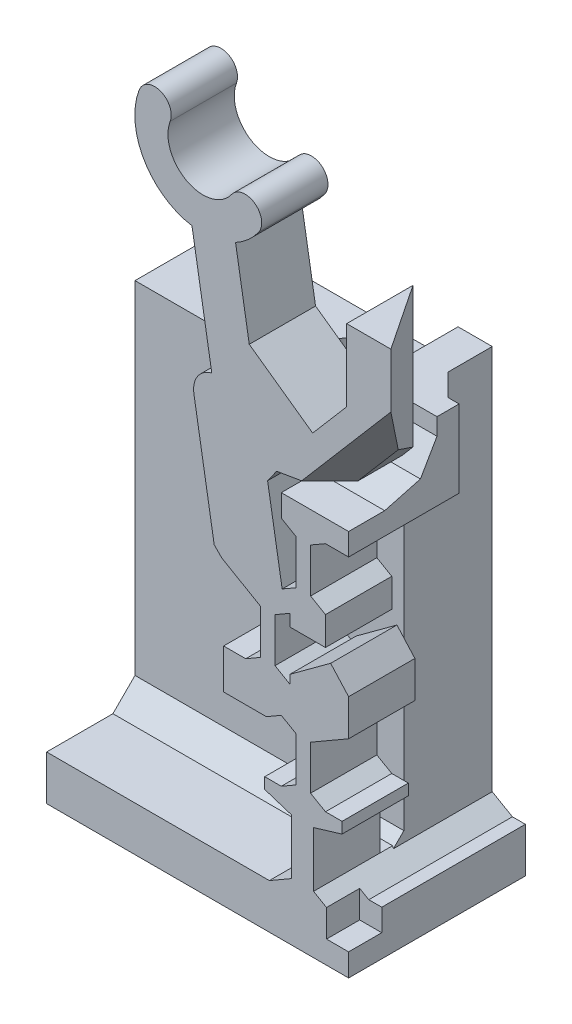
SolidWorks part; units mm, degrees
ref_plane "Front Plane" through (0, 0, 0) normal (0, 0, 1) x (1, 0, 0)
ref_plane "Top Plane" through (0, 0, 0) normal (0, 1, 0) x (1, 0, 0)
ref_plane "Right Plane" through (0, 0, 0) normal (1, 0, 0) x (0, 0, -1)
sketch "Sketch-SkeletonConfigUp" plane through (0, 0, 0) normal (0, 0, 1) x (1, 0, 0)
  line L0 (0, 0) -> (0, -50000) construction
  line L1 (0, 0) -> (4.5811, 6.2164) construction
  line L2 (9.8143, 13.3177) -> (4.5811, 13.945) construction
  line L3 (4.5811, 13.945) -> (2.9713, 10.4094) construction
  line L4 (2.9713, 10.4094) -> (4.5811, 6.2164) construction
  line L5 (4.5811, 13.945) -> (6.2429, 19.1409) construction
  line L6 (2.9713, 10.4094) -> (0.0405, 27.8193) construction
  line L7 (4.5811, 6.2164) -> (9.8143, 13.3177) construction
  line L8 (-587.3593, -797.0242) -> (9.8143, 13.3177) construction
  dimension "D2" = 7.7221
  dimension "D3" = 8.8212
  dimension "D4" = 5.2707
  dimension "D5" = 119.553
  dimension "D6" = 3.8848
  dimension "D7" = 5.4552
  dimension "D8" = 17.6549
  dimension "D9" = 4.4914
  dimension "D10" = 6.745
  dimension "D11" = 145.964
  dimension "D12" = 143.612
sketch "Sketch-SkeletonConfigDown" plane through (0, 0, 0) normal (0, 0, 1) x (1, 0, 0)
  line L0 (0, 0) -> (0, -50000) construction
  line L1 (0, 0) -> (4.5811, 6.2164) construction
  line L2 (9.8143, 13.3177) -> (4.5811, 13.945) construction
  line L3 (4.5811, 13.945) -> (6.1909, 10.4094) construction
  line L4 (6.1909, 10.4094) -> (4.5811, 6.2164) construction
  line L5 (4.5811, 13.945) -> (1.753, 18.6098) construction
  line L6 (6.1909, 10.4094) -> (-8.8652, 19.6294) construction
  line L7 (4.5811, 6.2164) -> (9.8143, 13.3177) construction
  line L8 (-589.9357, -800.5203) -> (9.8143, 13.3177) construction
  dimension "D2" = 7.7221
  dimension "D3" = 8.8212
  dimension "D4" = 5.2707
  dimension "D5" = 119.553
  dimension "D6" = 3.8848
  dimension "D7" = 5.4552
  dimension "D8" = 17.6549
  dimension "D9" = 4.4914
  dimension "D10" = 6.745
  dimension "D11" = 145.964
  dimension "D1" = 143.612
ref_plane "Plane-Cam Base" through (9.128, 0, 0) normal (1, 0, 0) x (0, 0, -1)
ref_plane "Plane-Down-to-Up Derailleur Clearance" through (6.628, 0, 0) normal (1, 0, 0) x (0, 0, -1)
ref_plane "Plane-Cam Cavity Roof" through (5.128, 0, 0) normal (1, 0, 0) x (0, 0, -1)
sketch "Sketch-SwitchBossUp" plane through (0, 0, 0) normal (0, 0, 1) x (1, 0, 0)
  line L0 (3.5811, 11.4759) -> (3.5811, 12.945) construction
  line L2 (6.5405, 21.1774) -> (6.5405, 24.4384)
  line L3 (6.5405, 24.4384) -> (8.5405, 24.4384)
  line L4 (8.5405, 24.4384) -> (8.5405, 20.4384)
  line L5 (5.5811, 12.5552) -> (5.5811, 11.263)
  line L7 (1.5115, 25.1048) -> (2.5464, 18.9575)
  line L8 (-0.4607, 24.7728) -> (0.4359, 19.4465)
  line L9 (2.9713, 10.4094) -> (0.0405, 27.8193) construction
  line L11 (-0.0396, 22.2712) -> (1.9326, 22.6032) construction
  line L15 (6.628, -23.7286) -> (6.628, 23.7286) construction
  line L16 (2.9713, 10.4094) -> (4.5811, 6.2164) construction
  line L17 (3.5811, 12.945) -> (3.5811, 14.945) construction
  line L18 (5.5811, 12.945) -> (5.5811, 14.945) construction
  line L19 (4.2561, 13.945) -> (4.9061, 13.945) construction
  line L20 (3.5811, 14.945) -> (5.5811, 14.945) construction
  line L21 (3.5811, 12.945) -> (5.5811, 12.945) construction
  line L22 (4.5811, 12.945) -> (4.5811, 14.945) construction
  line L23 (4.5811, 6.2164) -> (8.5405, 7.1023) construction
  line L24 (1.9713, 9.4094) -> (1.9713, 11.4094) construction
  line L25 (3.9713, 9.4094) -> (3.9713, 11.4094) construction
  line L26 (3.9713, 9.4094) -> (1.9713, 9.4094) construction
  line L27 (1.9713, 11.4094) -> (3.9713, 11.4094) construction
  line L28 (3.5811, 7.2164) -> (5.5811, 7.2164) construction
  line L29 (3.5811, 7.2164) -> (3.5811, 5.2164) construction
  line L30 (5.5811, 7.2164) -> (5.5811, 5.2164) construction
  line L31 (3.5811, 5.2164) -> (5.5811, 5.2164) construction
  line L32 (4.9061, 6.2164) -> (4.2561, 6.2164) construction
  line L40 (3.2963, 10.4094) -> (2.6463, 10.4094) construction
  line L43 (2.874, 4.5093) -> (0.7934, 4.5093) construction
  line L46 (5.0405, 1.437) -> (5.0405, 3.937)
  line L51 (4.9929, 19.3693) -> (2.5464, 18.9575)
  line L66 (0.0405, 27.8193) -> (0.0405, 50027.8193) construction
  line L74 (0.5455, 12.7717) -> (-0.3728, 18.2264)
  line L75 (0.3841, 13.7302) -> (2.3564, 14.0622) construction
  line L76 (5.5811, 11.263) -> (5.5811, 12.5552) construction
  line L77 (5.5811, 7.6061) -> (6.628, 8.2105)
  line L80 (5.8152, 10.763) -> (6.628, 9.8603)
  line L81 (8.5405, 1033.6218) -> (8.5405, 20.4384) construction
  line L82 (2.5464, 18.9575) -> (3.5585, 12.945) construction
  line L83 (3.6203, 12.5779) -> (2.8784, 16.9852)
  line L84 (2.8784, 16.9852) -> (6.0405, 17.5175)
  line L85 (6.9307, 9.5241) -> (8.5405, 7.7363) construction
  line L88 (3.5811, 16.3347) -> (6.8573, 16.3347)
  line L92 (3.7762, 8.3129) -> (6.9307, 9.5241) construction
  line L93 (6.3311, 4.3267) -> (5.0405, 3.937)
  line L95 (2.5464, 18.9575) -> (2.8784, 16.9852) construction
  line L96 (2.7124, 17.9713) -> (8.5405, 18.9524) construction
  line L97 (2.7124, 17.9713) -> (1.7262, 17.8053) construction
  line L98 (1.9713, 9.0197) -> (0.9713, 9.0197)
  line L99 (0.9713, 9.0197) -> (0.9713, 7.2164)
  line L100 (0.9713, 7.2164) -> (2.9061, 7.2164)
  line L101 (4.5811, 6.2164) -> (6.9307, 9.5241) construction
  line L103 (0.0405, 27.8193) -> (1.9448, 26.4638) construction
  line L104 (6.9307, 9.5241) -> (8.5405, 7.7363) construction
  line L106 (13.4416, 14.945) -> (5.5811, 14.945) construction
  line L107 (1.9713, 9.4094) -> (1.9713, 9.0197) construction
  line L109 (0.0405, 27.8193) -> (-2.1498, 28.6358) construction
  line L110 (8.5405, 20.4384) -> (6.0405, 17.5175)
  line L111 (6.628, 9.8603) -> (6.628, 8.2105)
  line L112 (6.628, 9.8603) -> (6.9307, 9.5241) construction
  line L113 (2.8311, 4.8267) -> (2.8311, 4.3267)
  line L114 (7.3693, 7.7363) -> (7.3563, 7.7363) construction
  line L115 (6.8573, 16.3347) -> (13.4416, 16.3347)
  line L116 (13.4416, 16.3347) -> (13.4416, -1.1653)
  line L117 (13.4416, -1.1653) -> (5.0405, -1.1653)
  line L119 (10.4375, 14.0252) -> (10.4375, 2.1692)
  line L121 (5.0405, -1.1653) -> (5.0405, 1.437) construction
  line L122 (8.237, 12.8031) -> (10.8393, 12.8031) construction
  line L123 (10.8393, 12.8031) -> (13.4416, 12.8031) construction
  line L124 (10.4375, 2.1692) -> (9.128, 0.8597)
  line L125 (8.5405, 7.5847) -> (13.4416, 7.5847) construction
  line L127 (5.5811, 15.3347) -> (5.5811, 14.945) construction
  line L130 (6.0405, 0.8597) -> (9.128, 0.8597)
  line L132 (2.8311, 4.3267) -> (4.0405, 3.937)
  line L133 (2.9713, 10.4094) -> (6.1909, 10.4094) construction
  line L134 (4.5811, 10.4094) -> (4.5811, 13.945) construction
  line L135 (4.5811, 10.4094) -> (4.5811, 6.2164) construction
  line L136 (0.8973, 12.4192) -> (0.5455, 12.7717)
  line L137 (3.9713, 9.4094) -> (5.5811, 7.2164) construction
  line L139 (5.8152, 10.763) -> (3.9713, 9.4094)
  line L140 (4.0405, 3.937) -> (4.0405, 1.437)
  line L141 (4.0405, 1.437) -> (3.0405, 0.8597)
  line L142 (3.0405, 0.8597) -> (3.0405, -1.1653)
  line L143 (8.5405, 20.4384) -> (8.5405, 18.9524) construction
  line L145 (8.5405, 17.9384) -> (8.5405, -49992.0368) construction
  line L147 (5.5811, 11.263) -> (5.5811, 12.5552) construction
  line L149 (6.3311, 4.8267) -> (6.3311, 4.3267)
  line L150 (3.0405, -1.1653) -> (5.0405, -1.1653)
  line L151 (4.0405, 3.937) -> (5.0405, 3.937) construction
  line L152 (4.2561, 14.945) -> (4.2561, 12.945)
  line L153 (4.9061, 14.945) -> (4.9061, 12.945)
  line L155 (4.2561, 14.945) -> (3.5811, 15.3347)
  line L156 (4.9061, 14.945) -> (5.5811, 15.3347)
  line L157 (3.5811, 16.3347) -> (3.5811, 15.3347)
  line L158 (5.5811, 15.3347) -> (9.128, 15.3347)
  line L162 (3.2963, 11.4094) -> (3.2963, 9.4094)
  line L164 (2.6463, 11.4094) -> (2.6463, 9.4094)
  line L169 (4.2561, 7.2164) -> (4.2561, 5.2164)
  line L170 (4.9061, 5.2164) -> (4.9061, 7.2164)
  line L175 (4.2561, 7.2164) -> (3.5811, 7.6061)
  line L176 (4.9061, 7.2164) -> (5.5811, 7.6061)
  line L177 (5.5811, 7.2164) -> (5.5811, 7.6061) construction
  line L179 (4.2561, 5.2164) -> (3.5811, 4.8267)
  line L180 (3.5811, 5.2164) -> (3.5811, 4.8267) construction
  line L181 (3.5811, 4.8267) -> (2.8311, 4.8267)
  line L183 (4.9061, 5.2164) -> (5.5811, 4.8267)
  line L184 (5.5811, 5.2164) -> (5.5811, 4.8267) construction
  line L186 (9.128, -23.7286) -> (9.128, 23.7286) construction
  line L187 (2.6463, 9.4094) -> (1.9713, 9.0197)
  line L188 (3.2963, 9.4094) -> (3.9713, 9.0197)
  line L189 (3.2963, 11.4094) -> (3.9713, 11.7991)
  line L190 (2.6463, 11.4094) -> (0.8973, 12.4192)
  line L191 (3.9713, 11.4094) -> (3.9713, 11.7991) construction
  line L192 (3.9713, 11.7991) -> (3.9713, 11.263)
  line L193 (4.9061, 12.945) -> (5.5811, 12.5552)
  line L194 (4.2561, 12.945) -> (3.6203, 12.5779)
  line L195 (3.9713, 11.263) -> (5.5811, 11.263)
  line L196 (3.9713, 9.4094) -> (3.9713, 9.0197)
  line L197 (3.5811, 7.2164) -> (3.5811, 7.6061) construction
  line L199 (3.5811, 7.6061) -> (2.9061, 7.2164)
  line L200 (5.5811, 4.8267) -> (6.3311, 4.8267)
  line L201 (2.8311, 4.3267) -> (2.8311, 3.937) construction
  line L202 (2.8311, 3.937) -> (4.0405, 3.937) construction
  line L203 (10.4375, 14.0252) -> (9.128, 15.3347)
  line L204 (4.0405, 1.437) -> (3.0405, 1.437) construction
  line L205 (3.0405, 1.437) -> (3.0405, 0.8597) construction
  line L206 (5.0405, 1.437) -> (6.0405, 0.8597)
  line L207 (8.5405, 18.9524) -> (8.5405, 17.9384) construction
  line L208 (6.0405, 17.5175) -> (8.5405, 17.9384) construction
  line L209 (8.5405, 20.4384) -> (8.5405, 17.9384) construction
  line L210 (6.5405, 21.1774) -> (4.9929, 19.3693)
  arc A0 (1.5115, 25.1048) -> (2.5558, 26.0289) centre (0.0405, 27.8193) ccw
  arc A1 (-0.4607, 24.7728) -> (-2.8525, 28.8978) centre (0.0405, 27.8193) cw
  arc A2 (-2.8525, 28.8978) -> (-1.447, 28.3738) centre (-2.1498, 28.6358) cw
  arc A3 (2.5558, 26.0289) -> (1.3338, 26.8987) centre (1.9448, 26.4638) ccw
  arc A4 (-1.447, 28.3738) -> (1.3338, 26.8987) centre (0.0405, 27.8193) ccw
  arc A5 (3.5811, 12.945) -> (3.5811, 14.945) centre (3.1778, 13.945) ccw construction
  arc A6 (5.5811, 12.945) -> (5.5811, 14.945) centre (5.9843, 13.945) cw construction
  arc A7 (2.5293, 9.921) -> (1.9713, 11.4094) centre (1.568, 10.4094) ccw construction
  arc A8 (3.9713, 11.4094) -> (3.9713, 9.4094) centre (4.3745, 10.4094) ccw construction
  arc A9 (3.5811, 7.2164) -> (3.5811, 5.2164) centre (3.1779, 6.2164) cw construction
  arc A10 (5.5811, 7.2164) -> (5.5811, 5.2164) centre (5.9844, 6.2164) ccw construction
  arc A19 (-0.3728, 18.2264) -> (0.4359, 19.4465) centre (0.6836, 18.4042) cw
  circle A28 centre (0.0405, 27.8193) radius 2.3375 construction
  arc A29 (1.9713, 9.4094) -> (2.5293, 9.921) centre (1.568, 10.4094) ccw construction
  point P53 (4.5811, 13.945)
  point P63 (2.9713, 10.4094)
  point P93 (0.9465, 22.4372)
  dimension "D23" = 1.5875
  dimension "D24" = 0.75
  dimension "D2" = 2
  dimension "D5" = 2
  dimension "D6" = 0.65
  dimension "D8" = 42
  dimension "D7" = 2
  dimension "D10" = 5
  dimension "D11" = 8.5
  dimension "D14" = 7.5
  dimension "D4" = 3
  dimension "D16" = 42
  dimension "D12" = 1
  dimension "D13" = 2.5
  dimension "D25" = 120
  dimension "D26" = 120
  dimension "D27" = 120
  dimension "D28" = 120
  dimension "D29" = 120
  dimension "D30" = 120
  dimension "D31" = 120
  dimension "D32" = 120
  dimension "D33" = 120
  dimension "D34" = 120
  dimension "D35" = 120
  dimension "D36" = 120
  dimension "D17" = 0.5
  dimension "D20" = 3.5
  dimension "D21" = 1
  dimension "D18" = 45
  dimension "D9" = 17.5
  dimension "D22" = 1
  dimension "D19" = 120
  dimension "D37" = 120
  dimension "D15" = 45
  dimension "D38" = 2
  dimension "D39" = 0.5
  dimension "D40" = 60
  dimension "D41" = 1
  dimension "D42" = 45
  dimension "D43" = 120
  dimension "D44" = 2
  dimension "D45" = 2.5
  dimension "D46" = 2.5
  dimension "D47" = 4
  dimension "D48" = 2
extrude "Boss-Switch Main" add sketch "Sketch-SwitchBossUp" along normal blind 3
sketch "Sketch1" plane through (0, 0, 0) normal (0, 0, -1) x (-1, 0, 0)
  line L0 (-3.5811, 16.3347) -> (-3.5811, 15.3347) construction
  line L1 (-7.5811, -1.1653) -> (0.4122, -1.1653)
  line L2 (-7.5811, -1.1653) -> (-7.5811, 0.8597)
  line L4 (0.4122, -1.1653) -> (0.4122, 0.8597)
  line L5 (-3.5811, 18.8347) -> (-7.5811, 18.8347)
  line L10 (-7.5811, 18.8347) -> (-7.5811, 15.3347)
  line L11 (-4.0405, 1.437) -> (-5.0405, 1.437)
  line L12 (-7.5811, 15.3347) -> (-3.5811, 15.3347)
  line L13 (-4.0405, 1.437) -> (-3.0405, 0.8597)
  line L14 (-3.5811, 15.3347) -> (-3.5811, 18.8347)
  line L22 (-3.0405, -1.1653) -> (-13.4416, -1.1653) construction
  line L23 (-3.0405, 0.8597) -> (0.4122, 0.8597)
  line L24 (-5.0405, 1.437) -> (-6.0405, 0.8597)
  line L25 (-6.0405, 0.8597) -> (-7.5811, 0.8597)
  line L26 (-9.128, 15.3347) -> (-5.5811, 15.3347) construction
  dimension "D1" = 3.5
  dimension "D4" = 4
extrude "Boss-Flange Width" add sketch "Sketch1" along normal blind 5
ref_plane "Plane-Sta2Sit Groove" through (0.0405, 0, 0) normal (1, 0, 0) x (0, 0, -1)
ref_plane "Plane-Cam Outer Surface" through (-12.0395, 0, 0) normal (1, 0, 0) x (0, 0, -1)
ref_plane "Plane-FlangeTop" through (-7.0395, 0, 0) normal (1, 0, 0) x (0, 0, -1)
sketch "Sketch2" plane through (-7.0395, 0, 0) normal (1, 0, 0) x (0, 0, -1)
  line L0 (5, 15.3347) -> (0, 15.3347) construction
  line L1 (5, 17.3347) -> (1, 17.3347)
  line L2 (5, 17.3347) -> (5, 15.3347)
  line L3 (5, 15.3347) -> (1, 15.3347)
  line L4 (1, 17.3347) -> (1, 15.3347)
  line L10 (-3, -1.1653) -> (-3, 16.3347) construction
  line L11 (5, 0.8597) -> (-3, 0.8597)
  line L12 (5, 0.8597) -> (5, -1.1653)
  line L13 (5, -1.1653) -> (-3, -1.1653)
  line L14 (-3, 0.8597) -> (-3, -1.1653)
  line L15 (0, 10.4094) -> (0, 27.8193) construction
  line L17 (5, 0.8597) -> (5, -1.1653) construction
  line L18 (-3, 0.8597) -> (0, 0.8597) construction
  dimension "D1" = 1
  dimension "D2" = 2
extrude "Boss-Flange Height" add sketch "Sketch2" along normal up to surface (11.6675 mm away)
sketch "Sketch10" plane through (0, 15.3347, 0) normal (0, 1, 0) x (1, 0, 0)
  line L0 (9.128, -23.7286) -> (9.128, 23.7286) construction
  line L1 (7.5811, 5) -> (5.128, 5)
  line L2 (7.5811, 5) -> (7.5811, 2)
  line L3 (7.5811, 2) -> (5.128, 2)
  line L5 (4.628, 7) -> (4.628, 1) construction
  line L6 (3.5811, 1) -> (-7.0395, 1) construction
  line L8 (5.128, 5) -> (5.128, 2)
  dimension "D1" = 1
  dimension "D2" = 0.5
  dimension "D3" = 4.5
extrude "Cut-Up-To-Down Derailleur Clearance" cut sketch "Sketch10" along normal up to next
sketch "Sketch17" plane through (0, 15.3347, 0) normal (0, -1, 0) x (1, 0, 0)
  line L0 (5.128, -5) -> (-7.0395, -5)
  line L1 (5.128, -5) -> (3.5811, -5) construction
  line L2 (-7.0395, -5) -> (-7.0395, -1)
  line L3 (-7.0395, -1) -> (5.128, -1)
  line L4 (5.128, -1) -> (5.128, -5)
  line L5 (-7.0395, -1) -> (-7.0395, -5) construction
extrude "Boss-Flange Support" add sketch "Sketch17" along normal up to surface (14.475 mm away) up to face at (-1.9995, 0.8597, -1)
sketch "Sketch-HolePositions" plane through (0, -1.1653, 0) normal (0, -1, 0) x (1, 0, 0)
  line L0 (-7.0395, -3) -> (7.5811, -3) construction
  line L1 (7.5811, -5) -> (-7.0395, -5) construction
  line L2 (7.5811, -5) -> (7.5811, 0) construction
  line L4 (-7.0395, -22.2167) -> (-7.0395, 22.2167) construction
  line L5 (3.5811, -1) -> (3.5811, -5) construction
  point P6 (-4.0395, -3)
  point P7 (0.5811, -3)
  dimension "D1" = 3
  dimension "D2" = 3
  dimension "D3" = 2
sketch "Sketch6" plane through (0, -1.1653, 0) normal (0, -1, 0) x (-1, 0, 0)
  point P0 (4.0395, 3)
  point P3 (-0.5811, 3)
hole_wizard "Tap Drill for M2x0.4 Tap1" positions "Sketch6" profile "Sketch5" hole size "M2x0.4" standard "ANSI Metric" end condition through all
sketch "Sketch5" plane through (-4.0395, -1.1653, -3) normal (1, 0, 0) x (0, 0, -1)
  line L0 (0, 0) -> (0, 30.5511)
  line L1 (0, 30.5511) -> (0.8, 30.5511)
  line L2 (0.8, 30.5511) -> (0.8, 0)
  line L5 (0.8, 0) -> (0, 0)
  line L11 (0, -6.35) -> (0, 107.95) construction
  dimension "Thru Hole Dia." = 1.6
  dimension "Thru Hole Depth" = 30.5511
sketch "Sketch9" plane through (0, -1.1653, 0) normal (0, -1, 0) x (1, 0, 0)
  point P0 (-4.0395, -3)
  point P3 (0.5811, -3)
hole_wizard "M2 Clearance Hole2" positions "Sketch9" profile "Sketch8" hole size "M2" standard "ANSI Metric"
sketch "Sketch8" plane through (-4.0395, -1.1653, -3) normal (1, 0, 0) x (0, 0, -1)
  line L0 (0, 0) -> (0, 15.721)
  line L1 (0, 15.721) -> (1.2, 15)
  line L2 (1.2, 15) -> (1.2, 0)
  line L5 (1.2, 0) -> (0, 0)
  line L10 (0, 15.721) -> (-1.2, 15) construction
  line L11 (0, -6.35) -> (0, 107.95) construction
  dimension "Hole Dia." = 2.4
  dimension "Hole Depth" = 15
  dimension "Drill Angle" = 118
sketch "Sketch-Measurements for Derailleur Ramps" plane through (0, 0, 0) normal (0, 0, 1) x (1, 0, 0)
  line L0 (2.8784, 16.9852) -> (2.5464, 18.9575)
  line L1 (2.7124, 17.9713) -> (1.7262, 17.8053)
  line L2 (2.9713, 10.4094) -> (0.0405, 27.8193) construction
  line L3 (1.7262, 17.8053) -> (-1.8937, 15.3603)
  line L4 (6.1909, 10.4094) -> (-8.8652, 19.6294) construction
  line L5 (1.7262, 17.8053) -> (2.6012, 12.6077)
  line L6 (2.6012, 12.6077) -> (-1.8937, 15.3603)
  line L7 (-0.0837, 16.5828) -> (-0.0837, 17.8053)
  line L8 (-0.0837, 17.8053) -> (1.7262, 17.8053)
  line L9 (6.1909, 10.4094) -> (2.9713, 10.4094)
  line L10 (5.386, 8.3129) -> (3.7762, 8.3129)
  line L12 (6.1909, 10.4094) -> (4.5811, 6.2164) construction
  line L13 (4.5811, 8.3129) -> (4.5811, 8.7912)
  line L14 (4.5811, 6.2164) -> (5.386, 8.3129)
  line L15 (2.9713, 10.4094) -> (4.5811, 6.2164) construction
  line L16 (3.7762, 8.3129) -> (4.5811, 6.2164)
  line L17 (5.386, 8.3129) -> (5.386, 8.7912)
  dimension "D1" = 1.81
  dimension "D2" = 0.8049
sketch "Sketch12" plane through (0, 24.4384, 0) normal (0, 1, 0) x (1, 0, 0)
  line L0 (6.5405, 0) -> (8.5405, -3)
  line L1 (8.5405, -3) -> (8.5405, 0)
  line L2 (8.5405, 0) -> (6.5405, 0)
extrude "Cut-Up-to-Down Cantilever Slope" cut sketch "Sketch12" against normal up to next
ref_plane "Plane1" through (0, 7.1023, 0) normal (0, 1, 0) x (1, 0, 0)
sketch "Sketch-Derailleur Location" plane through (0, 7.1023, 0) normal (0, 1, 0) x (1, 0, 0)
  line L0 (8.5405, 0) -> (8.5405, -3)
  line L1 (4.0405, -3) -> (3.0405, -3) construction
  line L2 (-119237.4187, 0) -> (9.8143, 0) construction
  point P0 (8.5405, 0)
  point P8 (8.5405, -1.5)
ref_plane "Plane-Cantilever Cut" [suppressed] through (7.0848, 8.5204, -1.9058) normal (-0.6301, -0.7578, 0.1695) x (-0.7765, 0.6151, -0.1368)
sketch "Sketch14" [suppressed] plane through (7.0848, 8.5204, -1.9058) normal (-0.6301, -0.7578, 0.1695) x (-0.7765, 0.6151, -0.1368)
  line L0 (2.3023, -1.6911) -> (-0.3551, -1.6911)
  line L2 (2.3023, -4.3362) -> (2.3023, -1.6911)
  line L3 (-0.3551, -1.6911) -> (-0.3551, -4.4608)
  line L5 (-0.3551, -4.4608) -> (1.0087, -5.0843)
  line L6 (1.0087, -5.0843) -> (2.3023, -4.3362)
extrude "Cut-Down-to-Up Cantilever Slope" [suppressed] cut sketch "Sketch14" against normal up to next
sketch "Sketch16" plane through (0, 0, 0) normal (0, 0, -1) x (-1, 0, 0)
  line L0 (-7.5811, 18.8347) -> (-13.4416, 18.8347)
  line L1 (-13.4416, 18.8347) -> (-13.4416, -1.1653)
  line L2 (-13.4416, -1.1653) -> (-6.628, -1.1653)
  line L3 (-13.4416, -1.1653) -> (-5.0405, -1.1653) construction
  line L4 (-6.628, -1.1653) -> (-6.628, 5.2038)
  line L5 (-6.628, 5.2038) -> (-8.0037, 5.2038)
  line L6 (-8.0037, 5.2038) -> (-8.0037, 12.0484)
  line L7 (-8.0037, 12.0484) -> (-6.628, 12.0484)
  line L8 (-6.628, 12.0484) -> (-6.628, 17.9477)
  line L9 (-6.628, 23.7286) -> (-6.628, -23.7286) construction
  line L10 (-3.5811, 18.8347) -> (-6.5405, 18.8347) construction
  line L11 (-7.5811, 18.8347) -> (-6.628, 17.9477)
extrude "Cut-Down-to-Up Derailleur Clearance" cut sketch "Sketch16" against normal through all and the other way through all
ref_plane "Plane-Symmetry Plane" through (0, 0, 1.5) normal (0, 0, 1) x (1, 0, 0)
sketch "Sketch-Cable Center Point" plane through (0, 0, 1.5) normal (0, 0, 1) x (1, 0, 0)
  line L0 (0.0405, 27.8193) -> (0.1722, 27.0366)
  line L1 (2.9713, 10.4094) -> (0.0405, 27.8193) construction
  point P0 (0.0405, 27.8193)
  dimension "D1" = 0.7937
chamfer "Chamfer-Flange Support" distance 1.5 angle 45 1 edges at (3.5811, 17.3347, -3)
chamfer "Chamfer-Flange Support 2" distance 1 angle 45 2 edges at (5.128, 17.0847, -2) (5.128, 15.3347, -1.5)
chamfer "Chamfer-Flange Support 3" distance 1 angle 45 1 edges at (-1.9995, 0.8597, -1)
sketch "Sketch18" plane through (6.628, 0, 0) normal (1, 0, 0) x (0, 0, -1)
  line L1 (-3, -0.1403) -> (-1.5, -0.1403)
  line L2 (-3, -0.1403) -> (-3, 1.437)
  line L3 (-3, 1.437) -> (-1.5, 1.437)
  line L4 (-1.5, -0.1403) -> (-1.5, 1.437)
  line L5 (0.5774, 1.437) -> (0, 1.437) construction
  line L6 (-3, -1.1653) -> (-3, 0.8597) construction
  line L7 (-3, 0.8597) -> (5, 0.8597) construction
  dimension "D1" = 1.5
  dimension "D2" = 1
extrude "Cut-Down-to-Up Derailleur Clearance 2" cut sketch "Sketch18" against normal blind 1
sketch "Sketch19" plane through (0, 0, 0) normal (0, 0, 1) x (1, 0, 0)
  line L7 (3.5811, 18.8347) -> (6.628, 18.8347)
  line L8 (6.628, 18.8347) -> (6.628, 16.3347)
  line L9 (6.628, 16.3347) -> (3.5811, 16.3347)
  line L10 (3.5811, 16.3347) -> (3.5811, 18.8347)
  line L11 (6.628, 16.3347) -> (6.628, 17.9477) construction
extrude "Cut-Up-to-Down Cantilever Clearance" cut sketch "Sketch19" against normal up to surface (1 mm away) up to face at (1.4435, 12.7784, -1)
chamfer "Chamfer1" distance 1 angle 60 1 edges at (5.1045, 16.3347, -1) first distance on face at (5.1045, 16.3347, 1)
chamfer "Chamfer3" distance 0.75 angle 60 1 edges at (3.5811, 16.7007, -1) first distance on face at (3.5811, 16.1233, 0.6667)
chamfer "Chamfer4" distance 0.5 angle 60 1 edges at (4.205, 15.3347, -1) first distance on face at (5.1242, 15.3347, -0.0278)
chamfer "Chamfer5" distance 0.5 angle 45 1 edges at (2.8784, 16.9852, 1.5)
chamfer "Chamfer6" distance 2.5 angle 45 1 edges at (2.5464, 18.9575, 1.5)
chamfer "Chamfer7" distance 1 angle 45 1 edges at (7.2905, 18.978, 3)
sketch "Sketch22" plane through (0, 0, 0) normal (0, 0, 1) x (1, 0, 0)
  line L0 (6.628, 17.9477) -> (7.5811, 18.8347) construction
  line L1 (6.628, 18.8347) -> (7.5811, 18.8347) construction
  line L2 (6.628, 17.9477) -> (6.628, 18.8347) construction
  line L3 (6.628, 17.9477) -> (7.5811, 18.8347)
  line L4 (6.628, 18.8347) -> (7.5811, 18.8347)
  line L5 (6.628, 17.9477) -> (6.628, 18.8347)
extrude "Cut-Extrude3" cut sketch "Sketch22" against normal up to next
chamfer "Chamfer8" distance 0.5 angle 45 1 edges at (5.1045, 16.3347, 0) first distance on face at (4.2965, 17.2286, -0.5161)
equation "\"axle-diameter\"=2"
equation "\"switch-thickness\"=12"
equation "\"base-width\"=4.0"
equation "\"axle-bushing-radius\"=3"
equation "\"clearance\"= 0.25"
equation "\"arm-width\"=1.5"
equation "\"min-diameter\"=70"
equation "\"alpha\"=143.6120"
equation "\"gamma\"=119.5526"
equation "\"delta\"=145.9637"
equation "\"epsilon\"=6.7452"
equation "\"l_AB\"=8.8212"
equation "\"l_AC\"=4.4914"
equation "\"l_BD\"=5.2707"
equation "\"l_CD\"=3.8848"
equation "\"l_CE\"=17.6549"
equation "\"l_DF\"=5.4552"
equation "\"l_OA\"=7.7221"
equation "\"D2@Sketch-SkeletonConfigUp\" = \"l_OA\""
equation "\"D3@Sketch-SkeletonConfigUp\" = \"l_AB\""
equation "\"D4@Sketch-SkeletonConfigUp\" = \"l_BD\""
equation "\"D5@Sketch-SkeletonConfigUp\" = \"gamma\""
equation "\"D6@Sketch-SkeletonConfigUp\" = \"l_CD\""
equation "\"D7@Sketch-SkeletonConfigUp\" = \"l_DF\""
equation "\"D8@Sketch-SkeletonConfigUp\" = \"l_CE\""
equation "\"D9@Sketch-SkeletonConfigUp\" = \"l_AC\""
equation "\"D_groove\"=3.175"
equation "\"D7@Sketch-SkeletonConfigDown\" = \"l_DF\""
equation "\"D6@Sketch-SkeletonConfigDown\" = \"l_CD\""
equation "\"D2@Sketch-SkeletonConfigDown\" = \"l_OA\""
equation "\"D3@Sketch-SkeletonConfigDown\" = \"l_AB\""
equation "\"D9@Sketch-SkeletonConfigDown\" = \"l_AC\""
equation "\"D8@Sketch-SkeletonConfigDown\" = \"l_CE\""
equation "\"D5@Sketch-SkeletonConfigDown\" = \"gamma\""
equation "\"D4@Sketch-SkeletonConfigDown\" = \"l_BD\""
equation "\"D1@Sketch-SkeletonConfigDown\" = \"alpha\""
equation "\"hinge_length\"=1.5"
equation "\"hinge_depth\"=0.25"
equation "\"D10@Sketch-SkeletonConfigUp\"=\"epsilon\""
equation "\"D11@Sketch-SkeletonConfigUp\"=\"delta\""
equation "\"D12@Sketch-SkeletonConfigUp\"=\"alpha\""
equation "\"D11@Sketch-SkeletonConfigDown\"=\"delta\""
equation "\"D10@Sketch-SkeletonConfigDown\"=\"epsilon\""
equation "\"EE_dx\"=8.9056"
equation "\"EE_dy\"=8.1898"
equation "\"r_groove\"=\"D_groove\"/2"
equation "\"t_wall\"=25.4/16"
equation "\"width_lower\"=\"D_groove\"+\"t_wall\""
equation "\"cable_to_bottom\"=30.6257"
equation "\"switch_EE-up_base_dy\"=24"
equation "\"switch_EE-down_base_dy\"=16"
equation "\"D_axle\"=25.4/8"
equation "\"D_up_to_down\"=16"
equation "\"D_down_to_up\"=25"
equation "\"t_cam_base\"=7.5"
equation "\"D23@Sketch-SwitchBossUp\"=\"D_groove\"/2"
equation "\"D1@Sketch-Cable Center Point\"=\"D_groove\"/4"
